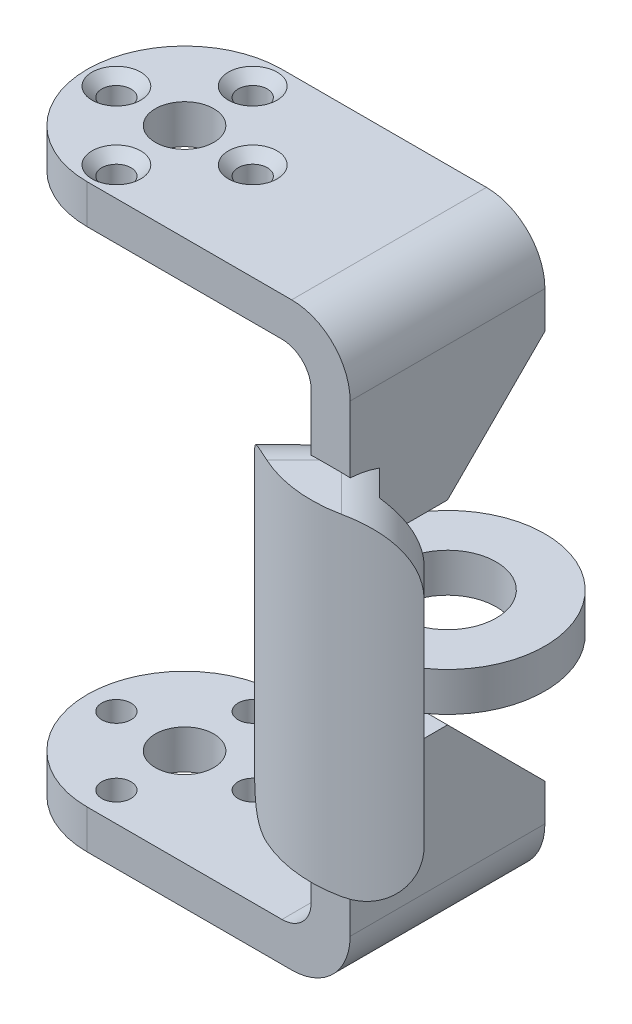
SolidWorks part; units mm, degrees
ref_plane "Спереди" through (0, 0, 0) normal (0, 0, 1) x (1, 0, 0)
ref_plane "Сверху" through (0, 0, 0) normal (0, 1, 0) x (1, 0, 0)
ref_plane "Справа" through (0, 0, 0) normal (1, 0, 0) x (0, 0, -1)
sketch "Sketch1" plane through (0, 0, 0) normal (0, 1, 0) x (1, 0, 0)
  line L1 (0, -10) -> (27, -10)
  line L2 (0, -10) -> (0, 10)
  line L3 (0, 10) -> (27, 10)
  line L4 (27, -10) -> (27, 10)
  circle A0 centre (0, 0) radius 10
  dimension "D1" = 20
  dimension "D2" = 20
  dimension "D3" = 27
extrude "Boss-Extrude1" add sketch "Sketch1" along normal blind 59.6 contours L2 A0 | L2 A0 | A0 L1 L4 L3 region at (17.2969, 0, 0) region at (-4.2441, 0, 0) region at (4.2441, 0, 0)
sketch "Sketch2" plane through (0, 0, 10) normal (0, 0, 1) x (1, 0, 0)
  line L0 (-10, 59.6) -> (-10, 0) construction
  line L1 (-10, 4) -> (23, 4)
  line L2 (-10, 4) -> (-10, 55.6)
  line L3 (-10, 55.6) -> (23, 55.6)
  line L4 (23, 4) -> (23, 55.6)
  line L5 (-10, 0) -> (0, 0) construction
  line L6 (0, 59.6) -> (-10, 59.6) construction
  line L7 (27, 59.6) -> (27, 0) construction
  dimension "D1" = 4
  dimension "D2" = 4
  dimension "D3" = 4
extrude "Cut-Extrude1" cut sketch "Sketch2" against normal blind 59.6
sketch "Sketch3" plane through (0, 59.6, 0) normal (0, 1, 0) x (1, 0, 0)
  circle A0 centre (0, 0) radius 7 construction
  circle A1 centre (-7, 0) radius 1.5
  circle A2 centre (0, 7) radius 1.5
  circle A3 centre (7, 0) radius 1.5
  circle A4 centre (0, -7) radius 1.5
  point P14 (0, 0)
  dimension "D1" = 14
  dimension "D2" = 3
  dimension "D3" = 4
extrude "Cut-Extrude2" cut sketch "Sketch3" against normal through all
chamfer "Chamfer1" distance 1 angle 45 8 edges at (-7, 0, 1.5) (0, 0, 8.5) (7, 0, 1.5) (0, 0, -5.5) (0, 59.6, -5.5) (7, 59.6, 1.5) (0, 59.6, 8.5) (-7, 59.6, 1.5)
sketch "Sketch4" plane through (0, 59.6, 0) normal (0, 1, 0) x (1, 0, 0)
  circle A0 centre (0, 0) radius 3
  dimension "D1" = 6
extrude "Cut-Extrude3" cut sketch "Sketch4" against normal through all
sketch "Sketch6" plane through (27, 0, 0) normal (1, 0, 0) x (0, 0, -1)
  line L0 (10, 59.6) -> (10, 0) construction
  line L1 (30, 19.8) -> (-10, 19.8)
  line L2 (30, 19.8) -> (30, 39.8)
  line L3 (30, 39.8) -> (-10, 39.8)
  line L4 (-10, 19.8) -> (-10, 39.8)
  line L5 (30, 19.8) -> (-10, 39.8) construction
  line L6 (30, 39.8) -> (-10, 19.8) construction
  line L7 (-10, 59.6) -> (-10, 0) construction
  point P0 (10, 29.8)
  dimension "D1" = 20
extrude "Cut-Extrude4" cut sketch "Sketch6" against normal blind 59.6
ref_plane "Plane1" through (0, 29.8, 0) normal (0, -1, 0) x (-1, 0, 0)
sketch "Sketch5" plane through (0, 29.8, 0) normal (0, -1, 0) x (-1, 0, 0)
  line L1 (-27, -10) -> (-27, 10) construction
  circle A1 centre (-27, 0) radius 10
  dimension "D1" = 20
extrude "Boss-Extrude2" add sketch "Sketch5" along normal mid plane 4 separate body
sketch "Sketch8" plane through (0, 29.8, 0) normal (0, -1, 0) x (-1, 0, 0)
  line L0 (-27, -10) -> (-27, 10) construction
  line L1 (-19.1676, -6.2172) -> (-16.3202, -9.0522)
  line L3 (-32.7728, -8.1655) -> (-35.6236, -11.0288)
  arc A0 (-32.7728, -8.1655) -> (-19.1676, -6.2172) centre (-27, 0) ccw
  arc A1 (-35.6236, -11.0288) -> (-16.3202, -9.0522) centre (-27, 0) ccw
  point P1 (0, 0)
  dimension "D1" = 28
extrude "Boss-Extrude3" add sketch "Sketch8" along normal mid plane 34
sketch "Sketch11" plane through (0, 27.8, 0) normal (0, -1, 0) x (1, 0, 0)
  circle A0 centre (27, 0) radius 5
  dimension "D1" = 10
extrude "Cut-Extrude5" cut sketch "Sketch11" against normal blind 4
fillet "Fillet1" radius 3 2 edges at (23, 55.6, 0) (23, 4, 0)
fillet "Fillet2" radius 6 6 edges at (17.7439, 12.8, 7.6347) (17.7439, 46.8, 7.6347) (34.1982, 46.8, 9.5971) (34.1982, 12.8, 9.5971) (27, 59.6, 0) (27, 0, 0)
chamfer "Chamfer2" distance 10 angle 45 2 edges at (25, 19.8, -10) (25, 39.8, -10)
chamfer "Chamfer3" distance 3 angle 45 4 edges at (27, 43.2842, 10) (27, 16.3158, 10) (23, 43.2387, 9.1652) (23, 16.3613, 9.1652) first distance on face at (27, 47.2281, 1.6667) first distance on face at (25.5618, 19.5795, 8.6905) first distance on face at (23, 46.8647, 2.6184)
